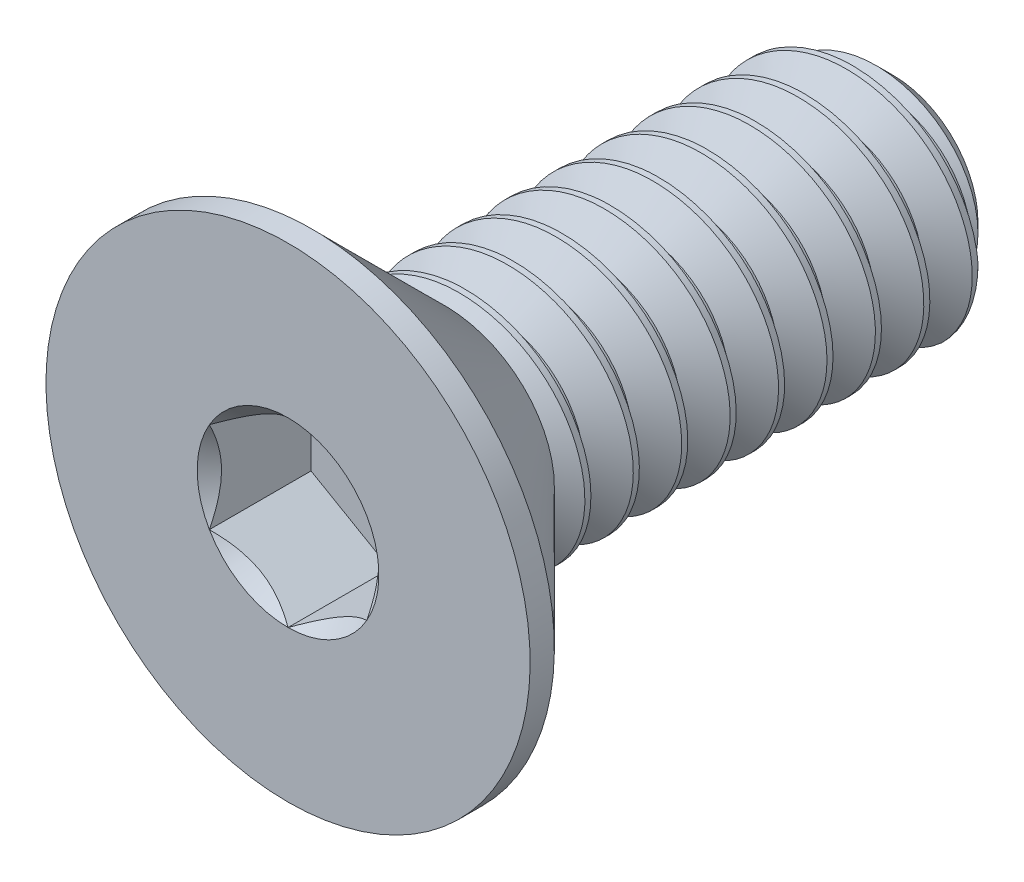
SolidWorks part; units mm, degrees
ref_plane "Front" through (0, 0, 0) normal (0, 0, 1) x (1, 0, 0)
ref_plane "Top" through (0, 0, 0) normal (0, 1, 0) x (1, 0, 0)
ref_plane "Right" through (0, 0, 0) normal (1, 0, 0) x (0, 0, -1)
sketch "Sketch1" plane through (0, 0, 0) normal (1, 0, 0) x (0, 0, -1)
  line L0 (0, 2) -> (0.2, 2) construction
  line L1 (0.2, 2) -> (1.2, 1) construction
  line L2 (0, 1) -> (5, 1)
  line L3 (5, 1) -> (5, 0)
  line L4 (5, 0) -> (0, 0)
  line L5 (0, 0) -> (0, 2) construction
  line L6 (0, 2) -> (0, -2) construction
  line L7 (5, 1) -> (5, -1) construction
  line L8 (0, -2) -> (0.2, -2) construction
  line L9 (0.2, -2) -> (1.2, -1) construction
  line L11 (0, 1) -> (0, 0)
  line L12 (1.2, 1) -> (1.2, 0) construction
revolve "Revolve1" add sketch "Sketch1" angle 360 mid plane about L4
sketch "Sketch3" plane through (0, 0, -5) normal (0, 0, -1) x (-1, 0, 0)
  circle A0 centre (0, 0) radius 1
curve "Helix/Spiral1" pitch 0.4 height 5 radius 1 centre (0, 0, -5) axis (0, 0, 1) start towards (0, 1, 0)
sketch "Sketch2" plane through (0, 0, 0) normal (1, 0, 0) x (0, 0, -1)
  line L0 (5, 1) -> (5.35, 1)
  line L1 (5.35, 1) -> (5.2, 0.7402)
  line L2 (5.2, 0.7402) -> (5.15, 0.7402)
  line L3 (5.15, 0.7402) -> (5, 1)
  line L4 (5.075, 0.8701) -> (5.275, 0.8701) construction
  dimension "D1" = 60
  dimension "D2" = 0.05
  dimension "D3" = 0.2
chamfer "Chamfer1" distance 0.3 angle 45 1 edges at (0, 1, -5)
sweep "Cut-Sweep1" cut profiles "Sketch2" path "Helix/Spiral1" align with end faces yes
sketch "Sketch7" plane through (0, 0, 0) normal (1, 0, 0) x (0, 0, -1)
  line L0 (0, 2) -> (0.2, 2) construction
  line L1 (0.2, 2) -> (1.2, 1) construction
  line L2 (0, 2) -> (0.2, 2)
  line L3 (0.2, 2) -> (1.2, 1)
  line L4 (1.2, 1) -> (1.2, 0) construction
  line L5 (1.2, 1) -> (1.2, 0)
  line L7 (0, 0) -> (0, 2) construction
  line L8 (0, 0) -> (0, 2)
  line L9 (0, 0) -> (1.2, 0)
  line L10 (2.2, 0) -> (-2.2, 0) construction
revolve "Revolve2" add sketch "Sketch7" angle 360 mid plane about L9
ref_plane "Plane1" through (0, 0, -1.2) normal (0, 0, 1) x (1, 0, 0)
sketch "Sketch8" plane through (0, 0, -1.2) normal (0, 0, 1) x (1, 0, 0)
  circle A0 centre (0, 0) radius 1
extrude "Boss-Extrude1" add sketch "Sketch8" against normal through all draft 45
sketch "Sketch5" plane through (0, 0, 0) normal (0, 0, 1) x (1, 0, 0)
  line L1 (0.65, -0.3753) -> (0.65, 0.3753)
  line L2 (0.65, 0.3753) -> (0, 0.7506)
  line L3 (0, 0.7506) -> (-0.65, 0.3753)
  line L4 (-0.65, 0.3753) -> (-0.65, -0.3753)
  line L5 (-0.65, -0.3753) -> (0, -0.7506)
  line L6 (0, -0.7506) -> (0.65, -0.3753)
  circle A0 centre (0, 0) radius 0.65 construction
  dimension "Hex" = 1.3
extrude "Cut-Extrude2" cut sketch "Sketch5" against normal blind 0.84
sketch "Sketch6" plane through (0, 0, 0) normal (0, 0, 1) x (1, 0, 0)
  circle A0 centre (0, 0) radius 0.7506
extrude "Cut-Extrude3" cut sketch "Sketch6" against normal blind 0.84 draft 45
sketch "Sketch9" [suppressed] plane through (0, 0, -5.5) normal (0, 0, 1) x (1, 0, 0)
  circle A1 centre (0, 0) radius 5
  circle A2 centre (0, 0) radius 5
  point P0 (0, 5)
  dimension "D1" = 0
extrude "Boss-Extrude2" [suppressed] add sketch "Sketch9" against normal offset from surface (18.5 mm away) 26 up to face at (0, 0.7, -5)
fillet "Fillet1" [suppressed] radius 0.2
sketch "Sketch10" plane through (0, 0, 0) normal (1, 0, 0) x (0, 0, -1)
  line L0 (5, 1) -> (5, -1) construction
  point P0 (4.4, -1)
  dimension "D1" = 0.6
equation "\"D3@Helix/Spiral1\" = \"Lg@Sketch1\""
equation "\"D2@Sketch2\" = \"D4@Helix/Spiral1\" * .125"
equation "\"D3@Sketch2\" = \"D4@Helix/Spiral1\" * .5"
equation "\"D1@Chamfer1\" = \"D4@Helix/Spiral1\" * .75"
equation "\"D1@Cut-Extrude2\" = \"Head Ht@Sketch1\" * .7"
equation "\"D1@Sketch10\" = \"D4@Helix/Spiral1\" * 1.5"
equation "\"D1@Cut-Extrude3\" = \"D1@Cut-Extrude2\""
equation "\"D1@Fillet1\" = \"Dia@Sketch1\" * .1"
